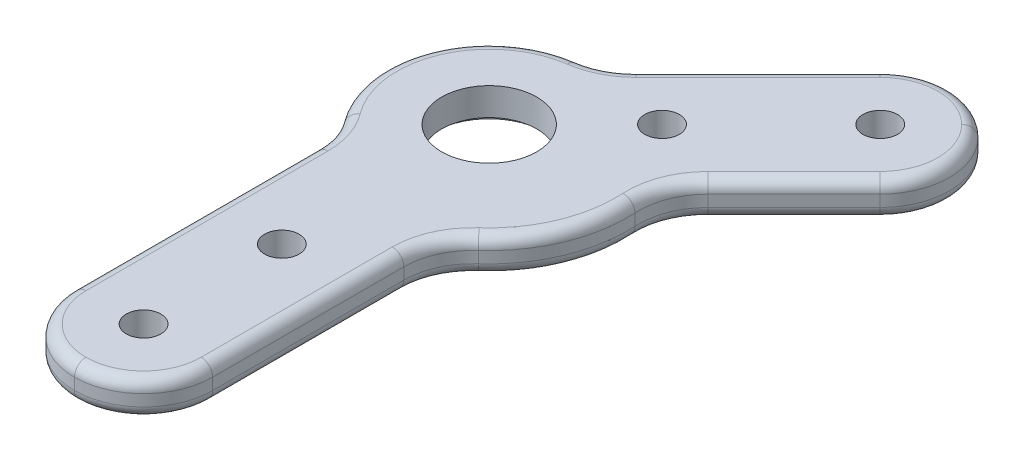
SolidWorks part; units mm, degrees
material "6061 Alloy"
ref_plane "Front Plane" through (0, 0, 0) normal (0, 0, 1) x (1, 0, 0)
ref_plane "Top Plane" through (0, 0, 0) normal (0, 1, 0) x (1, 0, 0)
ref_plane "Right Plane" through (0, 0, 0) normal (1, 0, 0) x (0, 0, -1)
sketch "Sketch1" plane through (0, 0, 0) normal (0, 1, 0) x (1, 0, 0)
  line L0 (0, 44.45) -> (0, -44.45) construction
  line L1 (-12.7, -44.45) -> (12.7, -44.45)
  line L2 (-12.7, -44.45) -> (-12.7, 31.75)
  line L3 (-12.7, 44.45) -> (12.7, 44.45) construction
  line L4 (12.7, -44.45) -> (12.7, 31.75)
  line L5 (-12.7, -44.45) -> (12.7, 44.45) construction
  line L6 (-12.7, 44.45) -> (12.7, -44.45) construction
  line L7 (0, 31.75) -> (44.9013, 76.6513) construction
  line L8 (8.9803, 22.7697) -> (53.8815, 67.671)
  line L9 (53.8815, 67.671) -> (35.921, 85.6315)
  line L10 (35.921, 85.6315) -> (-8.9803, 40.7303)
  line L11 (-8.9803, 40.7303) -> (8.9803, 22.7697) construction
  line L12 (12.7, 44.45) -> (12.7, 31.75) construction
  line L13 (53.8815, 67.671) -> (53.8815, -44.45) construction
  line L14 (53.8815, -44.45) -> (12.7, -44.45) construction
  line L15 (12.7, 44.45) -> (12.7, 62.4105) construction
  circle A0 centre (0, 31.75) radius 12.7 construction
  circle A1 centre (0, -31.75) radius 3.175
  circle A2 centre (0, -6.35) radius 3.175
  circle A3 centre (0, 31.75) radius 8.7312
  circle A4 centre (35.921, 67.671) radius 3.175
  circle A5 centre (15.875, 47.625) radius 3.175
  circle A6 centre (0, 31.75) radius 19.05
  arc A7 (24.5345, 38.324) -> (12.7, 9.753) centre (0, 31.75) cw
  point P0 (0, 0)
  point P16 (44.9013, 76.6513)
  point P21 (0, 31.75)
  dimension "D4" = 12.7
  dimension "D1" = 6.35
  dimension "D7" = 50.8
  dimension "D8" = 12.7
  dimension "D9" = 17.4625
  dimension "D10" = 6.35
  dimension "D11" = 6.35
  dimension "D2" = 25.4
  dimension "D3" = 45
  dimension "D5" = 25.4
  dimension "D6" = 38.1
extrude "Boss-Extrude1" add sketch "Sketch1" along normal blind 6.35 contours A0 L2 L1 L4 L8 A2 A1 | A0 L4 L8 L9 L10 A4 | A0 L8 L4 | L4 A6 L8 | A7 L8 A6 L4 region at (0, 0, 14.9202) region at (-17.1023, 0, -38.834) region at (19.6895, 0, -23.5944) region at (28.7883, 0, -60.5383) region at (15.553, 0, -25.3078)
fillet "Fillet2" radius 12.7 8 edges at (35.921, 3.175, -85.6315) (53.8815, 3.175, -67.671) (-12.7, 3.175, 44.45) (12.7, 3.175, 44.45) (1.06, 3.175, -50.7705) (-12.7, 3.175, -17.551) (12.7, 3.175, -9.753) (24.5345, 3.175, -38.324)
fillet "Fillet3" radius 2.1167 28 edges at (12.7, 0, 14.199) (8.9803, 0, 40.7303) (-8.9803, 0, 40.7303) (-12.7, 0, 9.525) (15.7154, 0, -65.426) (35.921, 0, -80.371) (48.621, 0, -67.671) (12.7, 6.35, 14.199) (8.9803, 6.35, 40.7303) (-8.9803, 6.35, 40.7303) (-12.7, 6.35, 9.525) (15.7154, 6.35, -65.426) (35.921, 6.35, -80.371) (48.621, 6.35, -67.671) (36.981, 0, -50.7705) (36.981, 6.35, -50.7705) (-17.5999, 0, -39.0401) (-13.3517, 0, -16.7161) (1.1895, 0, -51.8217) (-17.5999, 6.35, -39.0401) (-13.3517, 6.35, -16.7161) (1.1895, 6.35, -51.8217) (26.177, 0, -38.4016) (23.4665, 0, -22.0298) (13.8065, 0, -8.5367) (26.177, 6.35, -38.4016) (23.4665, 6.35, -22.0298) (13.8065, 6.35, -8.5367)
sketch "Sketch3" plane through (0, 0, 0) normal (0, -1, 0) x (1, 0, 0)
  circle A0 centre (0, -31.75) radius 10.2489
  dimension "D1" = 20.4978
extrude "Cut-Extrude1" cut sketch "Sketch3" against normal blind 1.27
